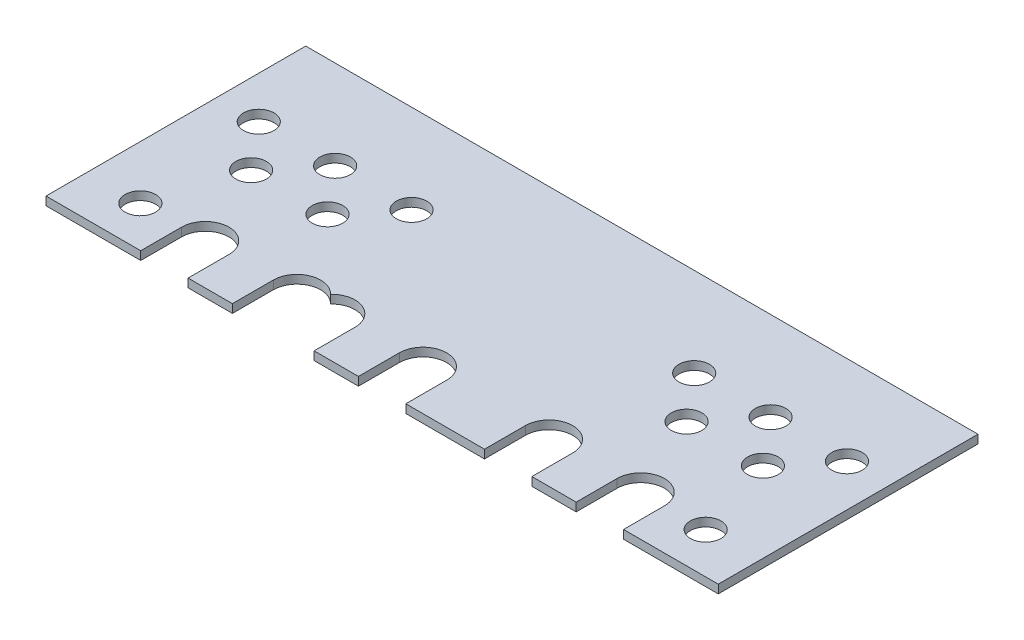
SolidWorks part; units mm, degrees
material "AISI 304"
ref_plane "Front Plane" through (0, 0, 0) normal (0, 0, 1) x (1, 0, 0)
ref_plane "Top Plane" through (0, 0, 0) normal (0, 1, 0) x (1, 0, 0)
ref_plane "Right Plane" through (0, 0, 0) normal (1, 0, 0) x (0, 0, -1)
sketch "Sketch1" plane through (0, 0, 0) normal (0, 1, 0) x (1, 0, 0)
  line L1 (44, -17) -> (-44, -17)
  line L2 (44, -17) -> (44, 17)
  line L3 (44, 17) -> (-44, 17)
  line L4 (-44, -17) -> (-44, 17)
  line L5 (44, -17) -> (-44, 17) construction
  line L6 (44, 17) -> (-44, -17) construction
  point P0 (0, 0)
  dimension "D1" = 88
  dimension "D2" = 34
extrude "Boss-Extrude1" add sketch "Sketch1" along normal blind 1.11
sketch "Sketch2" plane through (0, 1.11, 0) normal (0, 1, 0) x (1, 0, 0)
  line L0 (-44, 5.35) -> (44, 5.35) construction
  line L1 (-44, 17) -> (-44, -17) construction
  line L2 (44, -17) -> (44, 17) construction
  line L3 (44, -0.65) -> (-44, -0.65) construction
  line L4 (-44, -17) -> (44, -17) construction
  line L5 (-33.5, -0.65) -> (-33.5, 5.35) construction
  line L6 (-38.5, 5.35) -> (-28.5, 5.35) construction
  line L7 (28.5, 5.35) -> (38.5, 5.35) construction
  line L8 (33.5, 5.35) -> (33.5, -0.65) construction
  circle A0 centre (-38.5, 5.35) radius 2
  circle A1 centre (-28.5, 5.35) radius 2
  circle A2 centre (-18.5, 5.35) radius 2
  circle A3 centre (-33.5, -0.65) radius 2
  circle A4 centre (-23.5, -0.65) radius 2
  circle A6 centre (18.5, 5.35) radius 2
  circle A7 centre (28.5, 5.35) radius 2
  circle A8 centre (38.5, 5.35) radius 2
  circle A9 centre (23.5, -0.65) radius 2
  circle A10 centre (33.5, -0.65) radius 2
  dimension "D1" = 4
  dimension "D2" = 4
  dimension "D3" = 4
  dimension "D4" = 4
  dimension "D5" = 4
  dimension "D6" = 4
  dimension "D7" = 4
  dimension "D8" = 4
  dimension "D9" = 4
  dimension "D10" = 4
  dimension "D11" = 6
  dimension "D12" = 10
  dimension "D13" = 10
  dimension "D14" = 10
  dimension "D15" = 10
  dimension "D16" = 10
  dimension "D17" = 10
  dimension "D18" = 10.5
  dimension "D19" = 10.5
  dimension "D20" = 16.35
extrude "Cut-Extrude1" cut sketch "Sketch2" against normal through all
sketch "Sketch3" plane through (0, 1.11, 0) normal (0, 1, 0) x (1, 0, 0)
  line L0 (44, -17) -> (44, 17) construction
  line L1 (-44, 17) -> (-44, -17) construction
  line L2 (-44, -17) -> (44, -17) construction
  circle A0 centre (-37, -11.65) radius 2
  circle A1 centre (37, -11.65) radius 2
  dimension "D1" = 4
  dimension "D2" = 4
  dimension "D3" = 7
  dimension "D4" = 7
  dimension "D5" = 5.35
  dimension "D6" = 5.35
extrude "Cut-Extrude2" cut sketch "Sketch3" against normal through all
sketch "Sketch4" plane through (0, 1.11, 0) normal (0, 1, 0) x (1, 0, 0)
  line L0 (-31.6, -11.65) -> (-31.6, -17)
  line L1 (-44, -17) -> (44, -17) construction
  line L2 (-31.6, -17) -> (-25.4, -17)
  line L3 (-25.4, -17) -> (-25.4, -11.65)
  line L4 (-19.6, -11.65) -> (-19.6, -17)
  line L5 (-19.6, -17) -> (-8.9, -17)
  line L6 (-8.9, -11.65) -> (-8.9, -17)
  line L7 (13.4, -11.65) -> (13.4, -17)
  line L8 (13.4, -17) -> (19.6, -17)
  line L9 (19.6, -17) -> (19.6, -11.65)
  line L10 (25.4, -11.65) -> (25.4, -17)
  line L11 (25.4, -17) -> (31.6, -17)
  line L12 (31.6, -17) -> (31.6, -11.65)
  line L13 (-3.1, -11.65) -> (-3.1, -17)
  line L14 (-3.1, -17) -> (3.1, -17)
  line L15 (3.1, -17) -> (3.1, -11.65)
  line L16 (44, -17) -> (44, 17) construction
  line L17 (-44, -11.65) -> (44, -11.65) construction
  line L18 (-44, 17) -> (-44, -17) construction
  arc A0 (-25.4, -11.65) -> (-31.6, -11.65) centre (-28.5, -11.65) ccw
  arc A1 (-14.25, -9.5175) -> (-19.6, -11.65) centre (-16.5, -11.65) ccw
  arc A2 (19.6, -11.65) -> (13.4, -11.65) centre (16.5, -11.65) ccw
  arc A3 (31.6, -11.65) -> (25.4, -11.65) centre (28.5, -11.65) ccw
  arc A4 (3.1, -11.65) -> (-3.1, -11.65) centre (0, -11.65) ccw
  arc A5 (-14.25, -9.5175) -> (-8.9, -11.65) centre (-12, -11.65) cw
  dimension "D2" = 3.1
  dimension "D10" = 3.1
  dimension "D1" = 6.2
  dimension "D3" = 6.2
  dimension "D4" = 6.2
  dimension "D5" = 6.2
  dimension "D6" = 15.5
  dimension "D7" = 27.5
  dimension "D8" = 44
  dimension "D9" = 72.5
  dimension "D11" = 56
  dimension "D12" = 60.5
  dimension "D13" = 5.35
extrude "Cut-Extrude3" cut sketch "Sketch4" against normal through all
